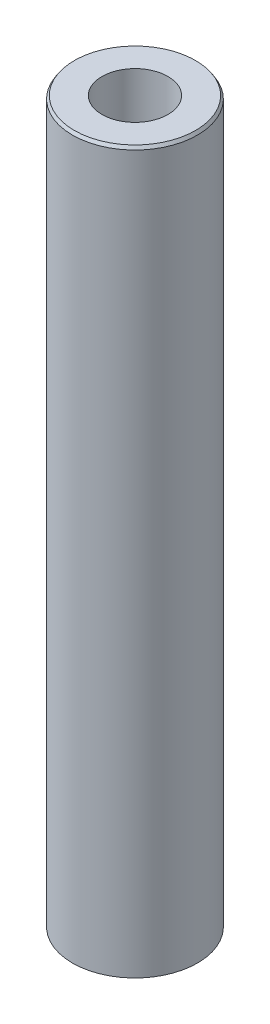
SolidWorks part; units mm, degrees
ref_plane "Front Plane" through (0, 0, 0) normal (0, 0, 1) x (1, 0, 0)
ref_plane "Top Plane" through (0, 0, 0) normal (0, 1, 0) x (1, 0, 0)
ref_plane "Right Plane" through (0, 0, 0) normal (1, 0, 0) x (0, 0, -1)
sketch "Sketch1" plane through (0, 0, 0) normal (0, 1, 0) x (1, 0, 0)
  circle A0 centre (0, 0) radius 40
  dimension "SHAFT_OD" = 80
extrude "Boss-Extrude1" add sketch "Sketch1" along normal blind 461.881
sketch "Sketch2" plane through (0, 0, 0) normal (0, 1, 0) x (1, 0, 0)
  circle A0 centre (0, 0) radius 21.0993
  dimension "BORE_D" = 42.1985
extrude "Cut-Extrude1" cut sketch "Sketch2" along normal through all
chamfer "Chamfer1" distance 1.9548 angle 32.039 2 edges at (0, 461.881, 40) (0, 0, 40) first distance on face at (0, 461.881, 40) first distance on face at (0, 0, 21.0993)
